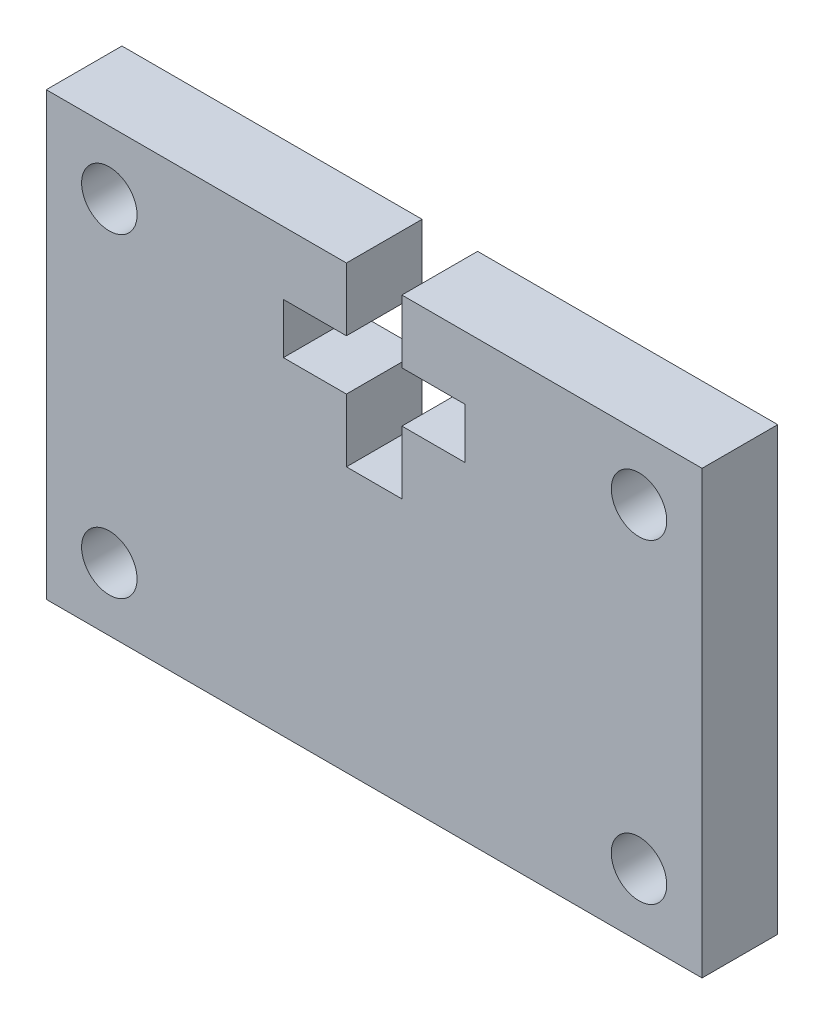
SolidWorks part; units mm, degrees
ref_plane "Front Plane" through (0, 0, 0) normal (0, 0, 1) x (1, 0, 0)
ref_plane "Top Plane" through (0, 0, 0) normal (0, 1, 0) x (1, 0, 0)
ref_plane "Right Plane" through (0, 0, 0) normal (1, 0, 0) x (0, 0, -1)
sketch "Sketch1" plane through (0, 0, 0) normal (0, 0, 1) x (1, 0, 0)
  line L0 (-13, 0) -> (13, 0) construction
  line L1 (-13, -8.75) -> (13, -8.75)
  line L2 (-13, -8.75) -> (-13, 8.75)
  line L3 (-13, 8.75) -> (13, 8.75) construction
  line L4 (13, -8.75) -> (13, 8.75)
  line L5 (-13, -8.75) -> (13, 8.75) construction
  line L6 (-13, 8.75) -> (13, -8.75) construction
  line L7 (-1.1, 8.75) -> (-1.1, 6.25)
  line L19 (0, 8.75) -> (0, -8.75) construction
  line L42 (-1.1, 6.25) -> (-3.6, 6.25)
  line L59 (-3.6, 6.25) -> (-3.6, 4.25)
  line L60 (-3.6, 4.25) -> (-1.1, 4.25)
  line L61 (-1.1, 4.25) -> (-1.1, 1.75)
  line L62 (-1.1, 1.75) -> (1.1, 1.75)
  line L63 (1.1, 4.25) -> (1.1, 1.75)
  line L64 (3.6, 4.25) -> (1.1, 4.25)
  line L65 (3.6, 6.25) -> (3.6, 4.25)
  line L66 (1.1, 6.25) -> (3.6, 6.25)
  line L67 (1.1, 8.75) -> (1.1, 6.25)
  line L68 (-13, 8.75) -> (-1.1, 8.75)
  line L69 (1.1, 8.75) -> (13, 8.75)
  circle A5 centre (-10.5, 6.25) radius 1.1
  circle A9 centre (-10.5, -6.25) radius 1.1
  circle A12 centre (10.5, -6.25) radius 1.1
  circle A13 centre (10.5, 6.25) radius 1.1
  point P0 (0, 0)
  point P20 (0, 1.75)
  dimension "D3" = 2.2
  dimension "D7" = 2.5
  dimension "D1" = 26
  dimension "D2" = 17.5
  dimension "D4" = 1.1
  dimension "D5" = 10.5
  dimension "D6" = 6.25
  dimension "D8" = 2
  dimension "D9" = 2.5
  dimension "D10" = 2.5
extrude "Boss-Extrude1" add sketch "Sketch1" along normal blind 3
